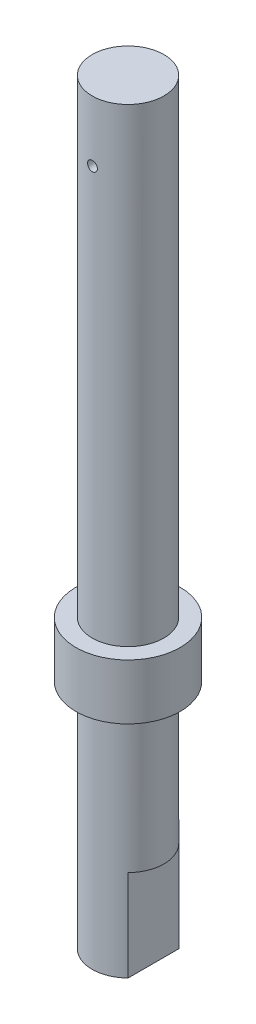
SolidWorks part; units mm, degrees
ref_plane "前视基准面" through (0, 0, 0) normal (0, 0, 1) x (1, 0, 0)
ref_plane "上视基准面" through (0, 0, 0) normal (0, 1, 0) x (1, 0, 0)
ref_plane "右视基准面" through (0, 0, 0) normal (1, 0, 0) x (0, 0, -1)
sketch "草图1" plane through (0, 0, 0) normal (0, 1, 0) x (1, 0, 0)
  circle A0 centre (0, 0) radius 2.75
  dimension "D1" = 5.5
extrude "凸台-拉伸1" add sketch "草图1" along normal blind 51
sketch "草图2" plane through (0, 0, 0) normal (0, -1, 0) x (1, 0, 0)
  line L0 (0, 0) -> (0, -4.8851) construction
  line L2 (-1.95, 1.9391) -> (-1.95, -1.9391)
  line L4 (1.95, 1.9391) -> (1.95, -1.9391)
  arc A0 (-1.95, -1.9391) -> (1.95, -1.9391) centre (0, 0) ccw
  arc A1 (1.95, 1.9391) -> (-1.95, 1.9391) centre (0, 0) ccw
  dimension "D1" = 5.5
  dimension "D2" = 3.9
extrude "凸台-拉伸2" add sketch "草图2" along normal blind 7
sketch "草图3" plane through (0, -7, 0) normal (0, -1, 0) x (1, 0, 0)
  circle A0 centre (0, 0) radius 4
  dimension "D1" = 8
extrude "凸台-拉伸3" add sketch "草图3" along normal blind 4.25 from offset 22 offset against normal yes
sketch "草图4" plane through (0, 0, 0) normal (0, 0, 1) x (1, 0, 0)
  circle A0 centre (0, 46.3457) radius 0.375
  dimension "D1" = 0.75
extrude "切除-拉伸1" cut sketch "草图4" against normal mid plane 10
